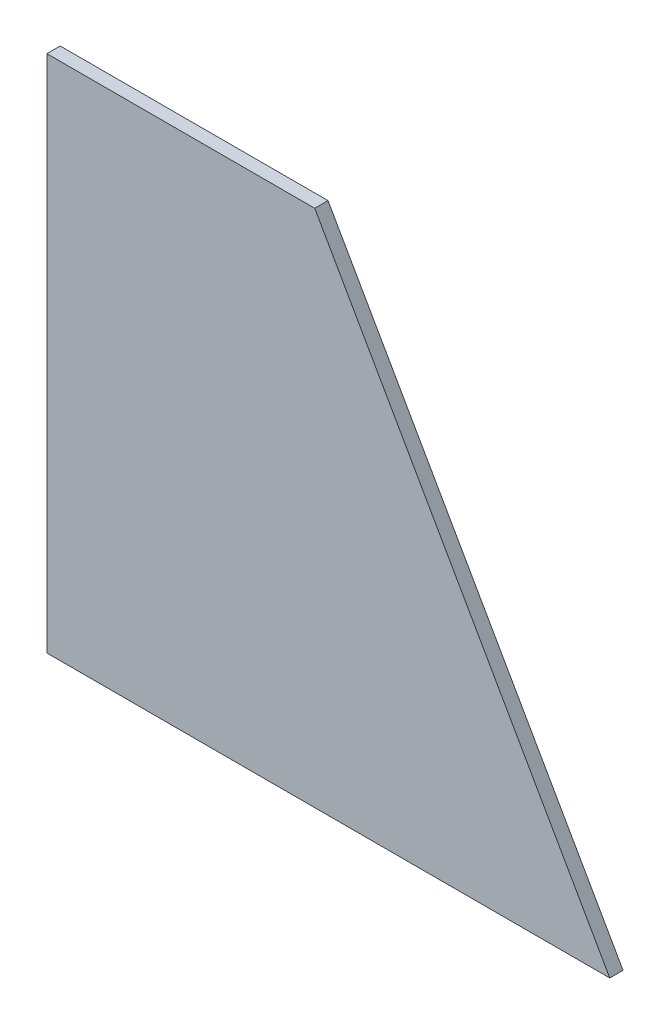
SolidWorks part; units mm, degrees
material "Pine"
ref_plane "Front Plane" through (0, 0, 0) normal (0, 0, 1) x (1, 0, 0)
ref_plane "Top Plane" through (0, 0, 0) normal (0, 1, 0) x (1, 0, 0)
ref_plane "Right Plane" through (0, 0, 0) normal (1, 0, 0) x (0, 0, -1)
sketch "Sketch1" plane through (0, 0, 0) normal (0, 0, 1) x (1, 0, 0)
  line L0 (-227.4281, 240.5594) -> (3.7119, 240.5594) construction
  line L1 (-227.4281, 240.5594) -> (12.5338, 240.5594)
  line L2 (-227.4281, 240.5594) -> (-227.4281, -224.5781)
  line L3 (-227.4281, -224.5781) -> (276.876, -224.5781)
  line L5 (-227.4281, -224.5781) -> (-227.4281, 215.8579) construction
  line L6 (-227.4281, 215.8579) -> (26.5719, 215.8579) construction
  line L7 (26.5719, 215.8579) -> (276.876, -224.5781)
  line L8 (26.5719, 215.8579) -> (12.5338, 240.5594)
  dimension "D1" = 465.1375
  dimension "D2" = 231.14
  dimension "D3" = 440.436
  dimension "D4" = 254
  dimension "D5" = 60.39
  dimension "D6" = 60.39
extrude "Boss-Extrude1" add sketch "Sketch1" along normal blind 11.9062
